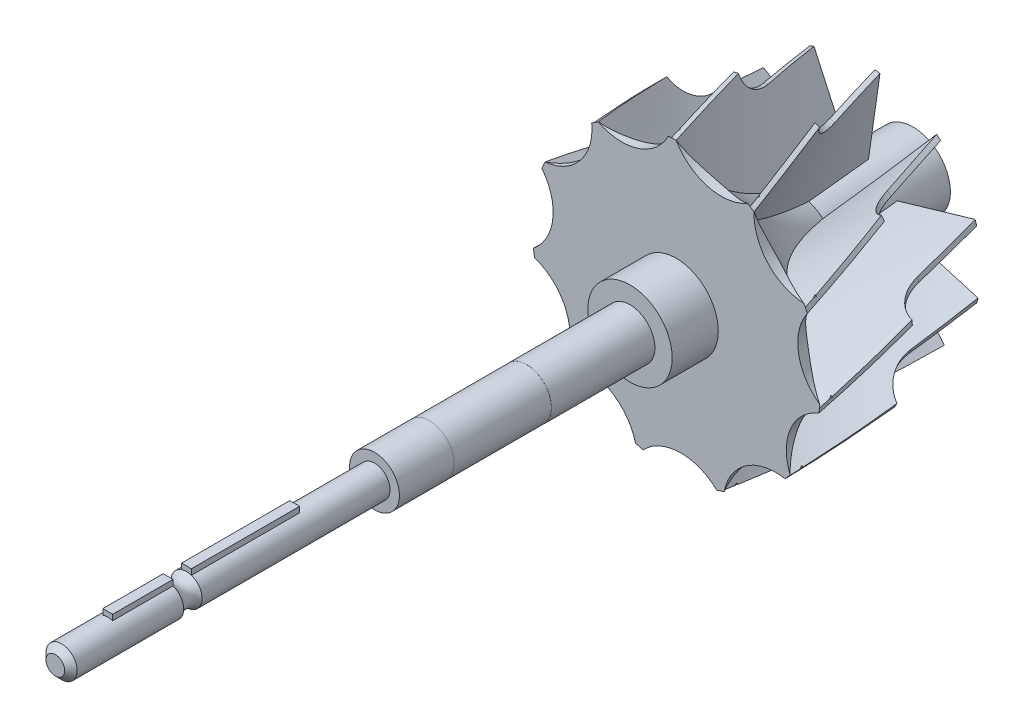
SolidWorks part; units mm, degrees
ref_plane "Alzado" through (0, 0, 0) normal (0, 0, 1) x (1, 0, 0)
ref_plane "Planta" through (0, 0, 0) normal (0, 1, 0) x (1, 0, 0)
ref_plane "Vista lateral" through (0, 0, 0) normal (1, 0, 0) x (0, 0, -1)
sketch "Croquis1" plane through (0, 0, 0) normal (0, 0, 1) x (1, 0, 0)
  circle A0 centre (0, 0) radius 7.62
  dimension "D1" = 15.24
extrude "Saliente-Extruir1" add sketch "Croquis1" along normal blind 38.1
sketch "Croquis2" plane through (0, 0, 38.1) normal (0, 0, 1) x (1, 0, 0)
  line L1 (0, 0) -> (-0.96, 0)
  line L2 (0, 0) -> (0, 30.48)
  line L3 (0, 30.48) -> (-0.96, 30.48)
  line L4 (-0.96, 0) -> (-0.96, 30.48)
  dimension "D1" = 30.48
  dimension "D2" = 0.96
sketch "Croquis3" plane through (0, 0, 0) normal (0, 0, -1) x (-1, 0, 0)
  line L0 (0, 0) -> (1.16, 0)
  line L1 (1.16, 0) -> (13.38, 26.7727)
  line L2 (13.38, 26.7727) -> (12.42, 27.2109)
  line L3 (12.42, 27.2109) -> (0, 0)
  dimension "D1" = 1.16
  dimension "D2" = 12.42
  dimension "D3" = 13.38
loft "Recubrir1" add profiles "Croquis3", "Croquis2" connector at (-13.38, 26.7727, 0) connector at (-0.96, 30.48, 38.1)
ref_axis "Eje1" through (0, 0, 38.0999) along (0, 0, -1)
pattern_circular "MatrizC1" count 11 over 360 about axis through (0, 0, 38.0999) along (0, 0, -1) of "Recubrir1"
sketch "Croquis4" plane through (0, 0, 0) normal (0, 1, 0) x (1, 0, 0)
  line L0 (-29.39, -38.84) -> (-39.3832, -38.84)
  line L1 (-39.3832, -38.84) -> (-39.3832, 8.47)
  line L2 (-39.3832, 8.47) -> (-19.629, 5.82)
  line L3 (-19.629, 5.82) -> (-23.31, 0)
  line L4 (-25.1597, 0) -> (-6.4095, 0) construction
  line L5 (-23.31, 0) -> (-24.109, 0)
  line L6 (-24.109, 0) -> (-24.109, -12.57)
  line L7 (-29.39, -38.84) -> (-29.39, -19.2931)
  line L8 (-29.9113, 0) -> (-7.62, 0) construction
  arc A0 (-24.109, -12.57) -> (-29.39, -19.2931) centre (-31.029, -12.57) cw
  dimension "D10" = 6.92
  dimension "D1" = 29.39
  dimension "D2" = 39.4142
  dimension "D3" = 38.84
  dimension "D4" = 5.82
  dimension "D5" = 8.47
  dimension "D6" = 19.66
  dimension "D7" = 23.31
  dimension "D8" = 31.06
  dimension "D9" = 12.57
revolve "Cortar-Revolución1" cut sketch "Croquis4" angle 360 about axis through (0, 0, 38.0999) along (0, 0, -1)
sketch "Croquis5" plane through (0, 0, 38.1) normal (0, 0, 1) x (1, 0, 0)
  circle A0 centre (0, 0) radius 8.59
  dimension "D1" = 17.18
extrude "Saliente-Extruir2" add sketch "Croquis5" along normal blind 12.7
sketch "Croquis6" plane through (0, 0, 50.8) normal (0, 0, 1) x (1, 0, 0)
  circle A0 centre (0, 0) radius 5.08
  dimension "D1" = 10.16
extrude "Saliente-Extruir3" add sketch "Croquis6" along normal blind 17.78
sketch "Croquis7" plane through (0, 0, 68.58) normal (0, 0, 1) x (1, 0, 0)
  circle A0 centre (0, 0) radius 5.065
  dimension "D1" = 10.13
extrude "Saliente-Extruir4" add sketch "Croquis7" along normal blind 19.812
sketch "Croquis8" plane through (0, 0, 88.392) normal (0, 0, 1) x (1, 0, 0)
  circle A0 centre (0, 0) radius 5.08
  dimension "D1" = 10.16
extrude "Saliente-Extruir5" add sketch "Croquis8" along normal blind 15.24
sketch "Croquis9" plane through (0, 0, 103.632) normal (0, 0, 1) x (1, 0, 0)
  circle A0 centre (0, 0) radius 3.175
  dimension "D1" = 6.35
extrude "Saliente-Extruir6" add sketch "Croquis9" along normal blind 60.96
sketch "Croquis10" plane through (0, 0, 0) normal (1, 0, 0) x (0, 0, -1)
  circle A0 centre (-139.74, 5.0516) radius 2.655
  dimension "D2" = 5.31
  dimension "D1" = 139.74
  dimension "D3" = 5.05
revolve "Cortar-Revolución2" cut sketch "Croquis10" angle 360 about axis through (0, 0, 38.0999) along (0, 0, -1)
sketch "Croquis11" plane through (0, 0, 0) normal (0, 0, -1) x (-1, 0, 0)
  circle A0 centre (0, 0) radius 7.62
  dimension "D1" = 15.24
extrude "Saliente-Extruir7" add sketch "Croquis11" along normal blind 10.16
sketch "Croquis12" plane through (0, 0, -10.16) normal (0, 0, -1) x (-1, 0, 0)
  circle A0 centre (0, 0) radius 1.27
  dimension "D1" = 2.54
extrude "Cortar-Extruir1" cut sketch "Croquis12" against normal blind 2.54
chamfer "Chaflán1" distance 1.27 angle 45 1 edges at (-1.27, 0, -10.16)
sketch "Croquis13" plane through (0, 0, 0) normal (1, 0, 0) x (0, 0, -1)
  line L0 (-38.1, 29.39) -> (-38.1, 1.7)
  line L1 (-38.1, -1.2225) -> (-38.1, 2.6728) construction
  line L2 (-38.1, 1.7) -> (0, 2.09)
  line L3 (0, 2.09) -> (0, 6.6)
  line L4 (0, 3.1937) -> (0, 11.7058) construction
  arc A0 (0, 6.6) -> (-38.1, 29.39) centre (-3.848, 43.4094) cw
  dimension "D1" = 37.01
  dimension "D2" = 27.3
  dimension "D3" = 22.79
  dimension "D4" = 27.69
revolve "Revolución1" add sketch "Croquis13" angle 360 about axis through (0, 0, 38.0999) along (0, 0, -1)
sketch "Croquis14" plane through (0, 0, 38.1) normal (0, 0, 1) x (1, 0, 0)
  line L0 (-15.8885, 24.725) -> (-15.8885, 30.1671)
  line L1 (-15.8885, 30.1671) -> (-3.76, 33.7771)
  line L2 (-3.76, 33.7771) -> (-1.5873, 29.3471)
  arc A0 (-15.8885, 24.725) -> (-1.5873, 29.3471) centre (-11.05, 34.19) ccw
  arc A1 (-16.6886, 24.1922) -> (-26.7341, 12.209) centre (0, 0) ccw construction
  arc A2 (-0.96, 29.3743) -> (-15.8894, 24.7244) centre (0, 0) ccw construction
  arc A3 (-28.9387, -5.1306) -> (-22.2115, -19.2464) centre (0, 0) ccw construction
  point P11 (-29.09, -4.1886)
  dimension "D2" = 10.63
  dimension "D1" = 34.19
  dimension "D3" = 11.05
  dimension "D4" = 29.09
  dimension "D5" = 25.33
  dimension "D6" = 0.82
  dimension "D7" = 4.43
extrude "Cortar-Extruir2" cut sketch "Croquis14" against normal blind 2.54
pattern_circular "MatrizC2" count 11 over 360 about axis through (0, 0, 38.0999) along (0, 0, -1) of "Cortar-Extruir2"
sketch "Croquis15" plane through (0, 0, 50.8) normal (0, 0, 1) x (1, 0, 0)
  circle A0 centre (0, 0) radius 8.89
  circle A1 centre (0, 0) radius 5.08
  dimension "D1" = 17.78
  dimension "D2" = 10.16
extrude "Cortar-Extruir3" cut sketch "Croquis15" against normal blind 3.302
sketch "Croquis16" plane through (0, 0, 103.632) normal (0, 0, 1) x (1, 0, 0)
  circle A0 centre (0, 0) radius 3.175
  circle A1 centre (0, 0) radius 5.865
  dimension "D1" = 11.73
  dimension "D2" = 6.35
extrude "Cortar-Extruir4" cut sketch "Croquis16" against normal blind 4.064
chamfer "Chaflán2" distance 1.27 angle 45 1 edges at (3.175, 0, 164.592)
ref_plane "Plano1" through (0, 0, 153.924) normal (0, 0, 1) x (1, 0, 0)
sketch "Croquis17" plane through (0, 0, 153.924) normal (0, 0, 1) x (1, 0, 0)
  line L0 (0, 0) -> (0, 3.175) construction
  line L1 (-1, 4.175) -> (1, 4.175)
  line L2 (-1, 4.175) -> (-1, 3.0134)
  line L4 (1, 4.175) -> (1, 3.0134)
  line L5 (-1, 4.175) -> (1, 2.175) construction
  line L6 (-1, 2.175) -> (1, 4.175) construction
  line L7 (1, 3.0134) -> (1, 2.175) construction
  line L8 (1, 2.175) -> (-1, 2.175) construction
  circle A0 centre (0, 0) radius 3.175 construction
  circle A1 centre (0, 0) radius 3.175 construction
  arc A2 (1, 3.0134) -> (-1, 3.0134) centre (0, 0) ccw
  point P0 (0, 3.175)
  dimension "D1" = 2
  dimension "D2" = 2
  dimension "D3" = 2
extrude "Saliente-Extruir8" add sketch "Croquis17" against normal blind 38.1
ref_plane "Plano2" through (0, 0, 141.6182) normal (0, 0, 1) x (1, 0, 0)
sketch "Croquis18" plane through (0, 0, 141.6182) normal (0, 0, 1) x (1, 0, 0)
  line L3 (-1, 4.175) -> (-1, 3.0134)
  line L4 (1, 3.0134) -> (1, 4.175)
  line L5 (1, 4.175) -> (-1, 4.175)
  line L6 (-1, 4.175) -> (-1, 3.0134)
  line L7 (1, 3.0134) -> (1, 4.175)
  line L8 (1, 4.175) -> (-1, 4.175)
  arc A1 (1, 3.0134) -> (-1, 3.0134) centre (0, 0) ccw
  arc A2 (1, 3.0134) -> (-1, 3.0134) centre (0, 0) ccw
  dimension "D1" = 0
extrude "Cortar-Extruir6" cut sketch "Croquis18" against normal up to vertex up to point (-1, 3.0134, 137.8618)
